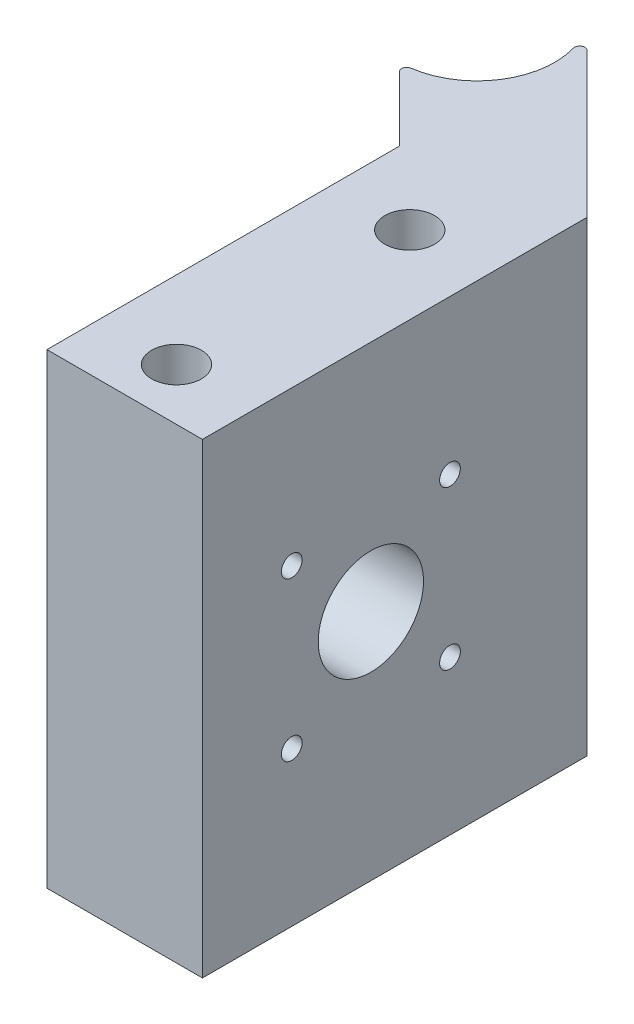
SolidWorks part; units mm, degrees
ref_plane "Front Plane" through (0, 0, 0) normal (0, 0, 1) x (1, 0, 0)
ref_plane "Top Plane" through (0, 0, 0) normal (0, 1, 0) x (1, 0, 0)
ref_plane "Right Plane" through (0, 0, 0) normal (1, 0, 0) x (0, 0, -1)
sketch "Sketch1" plane through (0, 0, 0) normal (0, 1, 0) x (1, 0, 0)
  line L0 (-14.5, 51) -> (7.5, 51) construction
  line L1 (7.5, 51) -> (7.5, 32.1066) construction
  line L2 (7.5, -5) -> (-7.5, -5)
  line L3 (-7.5, -5) -> (-7.5, 29)
  line L4 (-7.5, 36) -> (-14.5, 36) construction
  line L5 (0, 0) -> (0, -5) construction
  line L6 (-14.5, 36) -> (-7.5, 29)
  line L7 (-9.1967, 48.8033) -> (7.5, 32.1066)
  line L8 (-7.5, 29) -> (-7.5, 36) construction
  line L9 (7.5, 32.1066) -> (7.5, -5)
  circle A0 centre (0, 22.5) radius 2.4
  circle A1 centre (0, 0) radius 2.4
  arc A2 (-14.5, 36) -> (-9.1967, 48.8033) centre (-14.5, 43.5) ccw
  arc A3 (-9.1967, 48.8033) -> (-14.5, 51) centre (-14.5, 43.5) ccw construction
  dimension "D2" = 4.8
  dimension "D3" = 15
  dimension "D1" = 22.5
  dimension "D4" = 14.5
  dimension "D5" = 21
  dimension "D6" = 15
  dimension "D7" = 5
  dimension "D8" = 45
extrude "Boss-Extrude1" add sketch "Sketch1" along normal blind 45 contours A2 L6 L3 L2 L9 L7 A1 A0 region at (-0.8967, 0, -18.6724)
sketch "Sketch2" plane through (7.5, 0, 0) normal (1, 0, 0) x (0, 0, -1)
  line L0 (3.617, 30.133) -> (18.883, 14.867) construction
  line L1 (3.617, 30.133) -> (18.883, 30.133) construction
  line L2 (3.617, 30.133) -> (3.617, 14.867) construction
  line L3 (3.617, 14.867) -> (18.883, 14.867) construction
  line L4 (18.883, 30.133) -> (18.883, 14.867) construction
  line L5 (-5, 22.5) -> (11.25, 22.5) construction
  line L6 (-5, 45) -> (-5, 0) construction
  circle A0 centre (11.25, 22.5) radius 5.08
  circle A1 centre (3.617, 30.133) radius 1
  circle A2 centre (18.883, 30.133) radius 1
  circle A3 centre (18.883, 14.867) radius 1
  circle A4 centre (3.617, 14.867) radius 1
  dimension "D1" = 10.16
  dimension "D3" = 2
  dimension "D2" = 15.266
  dimension "D4" = 16.25
extrude "Cut-Extrude1" cut sketch "Sketch2" against normal up to next
fillet "Fillet1" radius 0.5 2 edges at (-9.1967, 22.5, -48.8033) (-14.5, 22.5, -36)
ref_plane "Plane1" through (0, 22.5, 0) normal (0, 1, 0) x (1, 0, 0)
sketch "Sketch3" plane through (0, 22.5, 0) normal (0, 1, 0) x (1, 0, 0)
  line L0 (-8.136, 37.136) -> (-2.8327, 42.4393)
  line L1 (-6.4581, 46.0647) -> (7.5, 32.1066) construction
  line L2 (-1.7721, 41.3787) -> (-7.0754, 36.0754)
  line L3 (-13.7263, 35.2263) -> (-7.5, 29) construction
  line L4 (-13.1083, 34.6083) -> (-11.842, 33.342)
  line L5 (-2.8327, 42.4393) -> (-1.7721, 41.3787)
  arc A0 (-13.1083, 34.6083) -> (-8.136, 37.136) centre (-14.5, 43.5) ccw
  arc A1 (-7.0754, 36.0754) -> (-11.842, 33.342) centre (-14.5, 43.5) cw
  dimension "D1" = 18
  dimension "D2" = 1.5
extrude "Cut-Extrude2" cut sketch "Sketch3" against normal mid plane 4
extrude "Cut-Extrude3" cut sketch "Sketch3<2>" against normal mid plane 4 from offset 17
sketch "Sketch3<2>" plane through (0, 22.5, 0) normal (0, 1, 0) x (1, 0, 0) same geometry as "Sketch3"
mirror "Mirror1" about plane through (0, 22.5, 0) normal (0, 1, 0) of "Cut-Extrude3"
